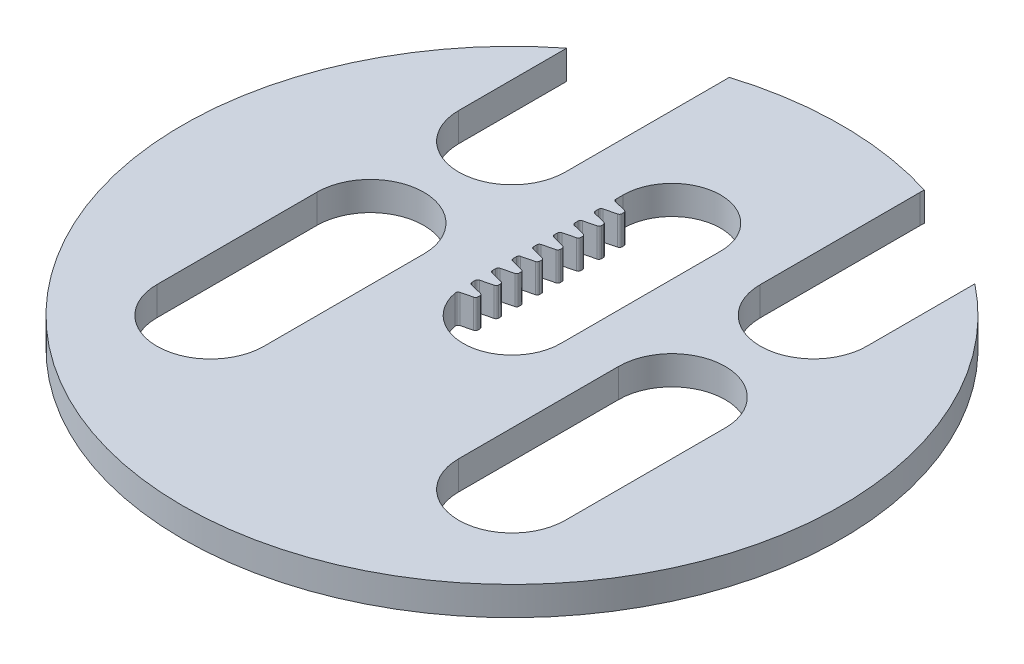
SolidWorks part; units mm, degrees
ref_plane "Front Plane" through (0, 0, 0) normal (0, 0, 1) x (1, 0, 0)
ref_plane "Top Plane" through (0, 0, 0) normal (0, 1, 0) x (1, 0, 0)
ref_plane "Right Plane" through (0, 0, 0) normal (1, 0, 0) x (0, 0, -1)
sketch "Sketch3" plane through (0, 0, 0) normal (0, -1, 0) x (1, 0, 0)
  line L0 (0, 0) -> (0, -19.05) construction
  line L1 (5.8, 0) -> (5.8, -19.05)
  line L2 (-5.8, 0) -> (-5.8, -19.05)
  line L3 (-17.9605, -37.0105) -> (17.9605, -1.0895) construction
  line L4 (-17.9605, -1.0895) -> (17.9605, -37.0105) construction
  line L5 (-17.9605, -1.0895) -> (17.9605, -1.0895) construction
  line L6 (-17.9605, -1.0895) -> (-17.9605, 17.9605) construction
  line L7 (-24.3305, -1.0895) -> (-24.3305, 17.9605)
  line L8 (-11.5905, -1.0895) -> (-11.5905, 17.9605)
  line L9 (-17.9605, -37.0105) -> (-17.9605, -17.9605) construction
  line L10 (-24.3105, -37.0105) -> (-24.3105, -17.9605)
  line L11 (-11.6105, -37.0105) -> (-11.6105, -17.9605)
  line L12 (17.9605, -1.0895) -> (17.9605, 17.9605) construction
  line L13 (11.6105, -1.0895) -> (11.6105, 17.9605)
  line L14 (24.3105, -1.0895) -> (24.3105, 17.9605)
  line L15 (17.9605, -37.0105) -> (17.9605, -17.9605) construction
  line L16 (11.6105, -37.0105) -> (11.6105, -17.9605)
  line L17 (24.3105, -37.0105) -> (24.3105, -17.9605)
  circle A0 centre (0, 0) radius 39.2557
  arc A1 (5.8, 0) -> (-5.8, 0) centre (0, 0) ccw
  arc A2 (-5.8, -19.05) -> (5.8, -19.05) centre (0, -19.05) ccw
  arc A3 (-24.3305, -1.0895) -> (-11.5905, -1.0895) centre (-17.9605, -1.0895) ccw
  arc A4 (-11.5905, 17.9605) -> (-24.3305, 17.9605) centre (-17.9605, 17.9605) ccw
  arc A5 (-24.3105, -37.0105) -> (-11.6105, -37.0105) centre (-17.9605, -37.0105) ccw
  arc A6 (-11.6105, -17.9605) -> (-24.3105, -17.9605) centre (-17.9605, -17.9605) ccw
  arc A7 (11.6105, -1.0895) -> (24.3105, -1.0895) centre (17.9605, -1.0895) ccw
  arc A8 (24.3105, 17.9605) -> (11.6105, 17.9605) centre (17.9605, 17.9605) ccw
  arc A9 (11.6105, -37.0105) -> (24.3105, -37.0105) centre (17.9605, -37.0105) ccw
  arc A10 (24.3105, -17.9605) -> (11.6105, -17.9605) centre (17.9605, -17.9605) ccw
  point P5 (0, -9.525)
  point P10 (-17.9605, 8.4355)
  point P13 (0, -19.05)
  point P16 (0, -19.05)
  point P22 (-17.9605, -27.4855)
  point P28 (17.9605, 8.4355)
  point P34 (17.9605, -27.4855)
  dimension "D1" = 78.5114
  dimension "D3" = 5.8
  dimension "D8" = 6.37
  dimension "D10" = 6.35
  dimension "D13" = 6.35
  dimension "D14" = 6.35
  dimension "D2" = 19.05
  dimension "D4" = 45
  dimension "D5" = 45
  dimension "D6" = 50.8
extrude "Boss-Extrude1" add sketch "Sketch3" along normal blind 3.175 and the other way blind 0.254 contours L17 A10 L16 A0 L11 A6 L10 L2 A2 L1 A1 L8 A4 L7 A3 L14 A8 L13 A7 region at (-16.6428, 0, 34.3233)
sketch "Sketch4" plane through (0, 0.254, 0) normal (0, 1, 0) x (1, 0, 0)
  line L0 (-5.8, 0) -> (-3.94, 0) construction
  line L1 (-3.94, -0.34) -> (-3.94, 0.34)
  line L2 (-3.94, 0.34) -> (-5.8, 0.8038)
  line L3 (-5.8, 0) -> (-5.8, 19.05) construction
  line L8 (-5.8, 0.8038) -> (-5.8, -0.8038)
  line L9 (-5.8, -0.8038) -> (-3.94, -0.34)
  point P7 (-3.94, 0)
  line M5 (-5.8, 0) -> (-5.8, 19.05)
  arc M8 (5.8, 0) -> (-5.8, 0) centre (0, 0) cw
  dimension "D3" = 76
  dimension "D1" = 1.86
  dimension "D2" = 0.34
extrude "Boss-Extrude2" add sketch "Sketch4" against normal up to surface (3.429 mm away) contours L1 L2 M5 M8 | L0 L9 L1 M8 | L8 L9 M8 region at (-4.9957, 0.254, -0.3016) region at (-5.7837, 0.254, 0.5979) region at (-4.9847, 0.254, 0.2975) up to face at (0, -3.175, -9.525)
pattern_linear "LPattern1" count 8 spacing 2.45 along (0, 0, -1) of "Boss-Extrude2"
fillet "Fillet1" radius 0.3 32 edges at (-3.94, -1.4605, 0.34) (-5.8, -1.4605, -1.6462) (-3.94, -1.4605, -2.11) (-3.94, -1.4605, -2.79) (-5.8, -1.4605, -3.2538) (-5.8, -1.4605, -4.0962) (-3.94, -1.4605, -4.56) (-3.94, -1.4605, -5.24) (-5.8, -1.4605, -5.7038) (-5.8, -1.4605, -6.5462) (-3.94, -1.4605, -7.01) (-3.94, -1.4605, -7.69) (-5.8, -1.4605, -8.1538) (-5.8, -1.4605, -8.9962) (-3.94, -1.4605, -9.46) (-3.94, -1.4605, -10.14) (-5.8, -1.4605, -10.6038) (-5.8, -1.4605, -11.4462) (-3.94, -1.4605, -11.91) (-3.94, -1.4605, -12.59) (-5.8, -1.4605, -13.0538) (-5.8, -1.4605, -13.8962) (-3.94, -1.4605, -14.36) (-3.94, -1.4605, -15.04) (-5.8, -1.4605, -15.5038) (-5.8, -1.4605, -16.3462) (-3.94, -1.4605, -16.81) (-3.94, -1.4605, -17.49) (-5.8, -1.4605, -17.9538) (-5.7459, -1.4605, 0.7903) (-5.8, -1.4605, -0.8038) (-3.94, -1.4605, -0.34)
equation "\"AIRFRAME_OD\"= 3.091in"
equation "\"AIRFRAME_ID\"= 3.00in"
equation "\"FLAT_T\"= 0.125in"
equation "\"COUPLER_OD\"= 2.998in"
equation "\"COUPLER_ID\"= 2.875in"
equation "\"NOSE_EXP_L\"= 3.5in"
equation "\"NOSE_SHOULDER_L\"= 5in"
equation "\"MAIN_L\"= 26in"
equation "\"RECO_COUP_L\"= 6in"
equation "\"RECO_SWITCH_L\"= 1.5in"
equation "\"RECO_ROD_X\"= 1.5in"
equation "\"DROGUE_L\"= 14in"
equation "\"ATS_FORE_COUP_L\"= 4in"
equation "\"ATS_AFT_COUP_L\"= 4in"
equation "\"ATS_ROD_X\"= 2in"
equation "\"LOWER_L\"= 16in"
equation "\"FIN_ROOT\"= 5in"
equation "\"FIN_X\"= 0.75in"
equation "\"FIN_N\"= 4"
equation "\"MOTOR_OD\"= 2.25in"
equation "\"MOTOR_ID\"= 2.126in"
equation "\"MOTOR_L\"= 8in"
equation "\"MOTOR_LOWER_X\"= 0.5in"
equation "\"CR_AFT_X\"= 0.5in"
equation "\"CR_FORE_X\"= 6in"
equation "\"D1@Boss-Extrude1\"=\"FLAT_T\""
equation "\"D1@Sketch3\"=\"AIRFRAME_OD\""
equation "\"D6@Sketch3\"=\"ATS_ROD_X\""
